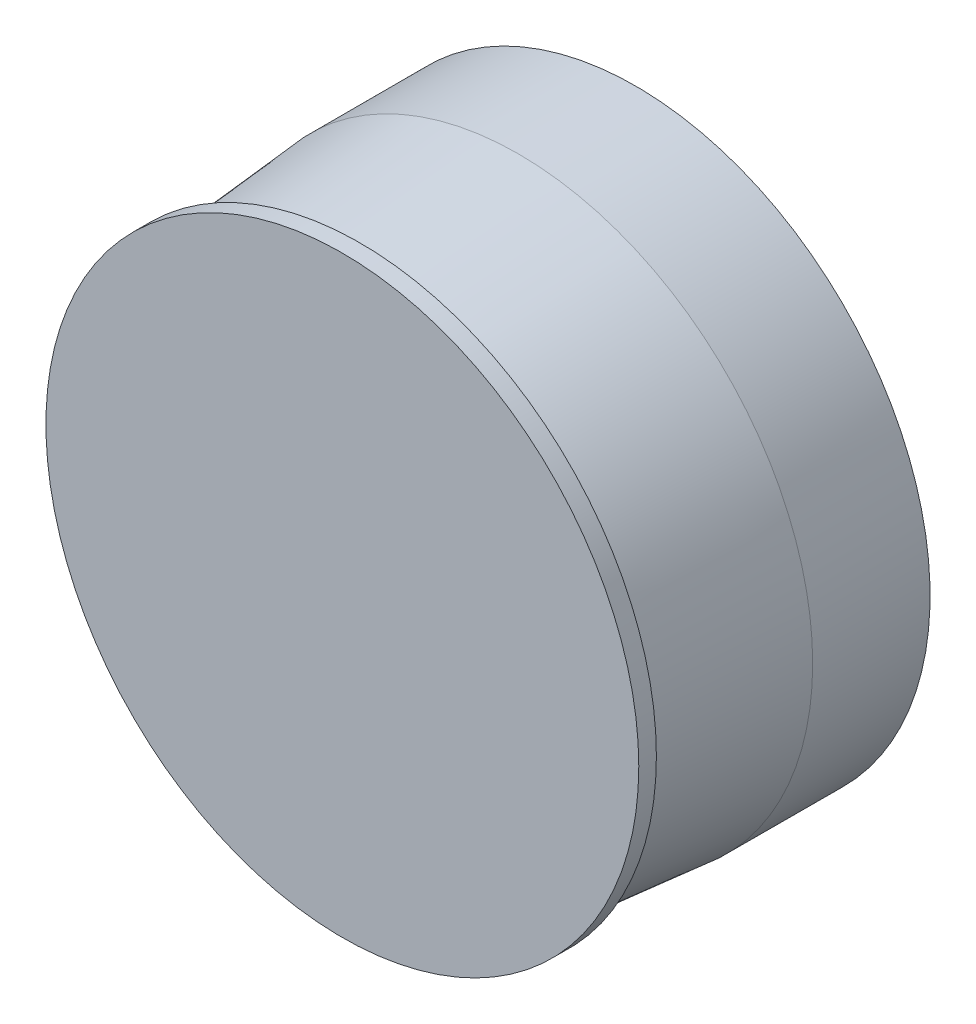
SolidWorks part; units mm, degrees
ref_plane "Front Plane" through (0, 0, 0) normal (0, 0, 1) x (1, 0, 0)
ref_plane "Top Plane" through (0, 0, 0) normal (0, 1, 0) x (1, 0, 0)
ref_plane "Right Plane" through (0, 0, 0) normal (1, 0, 0) x (0, 0, -1)
sketch "Sketch1" plane through (0, 0, 0) normal (0, 0, 1) x (1, 0, 0)
  circle A0 centre (0, 0) radius 47.5
  circle A1 centre (0, 0) radius 50.5
  dimension "D1" = 95
  dimension "D2" = 3
extrude "Boss-Extrude1" add sketch "Sketch1" against normal blind 30 draft 5 contours A0 region at (0, 0, 0) draft outward yes
extrude "Boss-Extrude2" add sketch "Sketch1<3>" against normal blind 3 contours A1
sketch "Sketch1<3>" plane through (0, 0, 0) normal (0, 0, 1) x (1, 0, 0) same geometry as "Sketch1"
sketch "Sketch2" plane through (0, 0, -30) normal (0, 0, -1) x (-1, 0, 0)
  circle A1 centre (0, 0) radius 50.1247
  circle A2 centre (0, 0) radius 50.1247
  dimension "D1" = 0
extrude "Boss-Extrude3" add sketch "Sketch2" along normal blind 20
